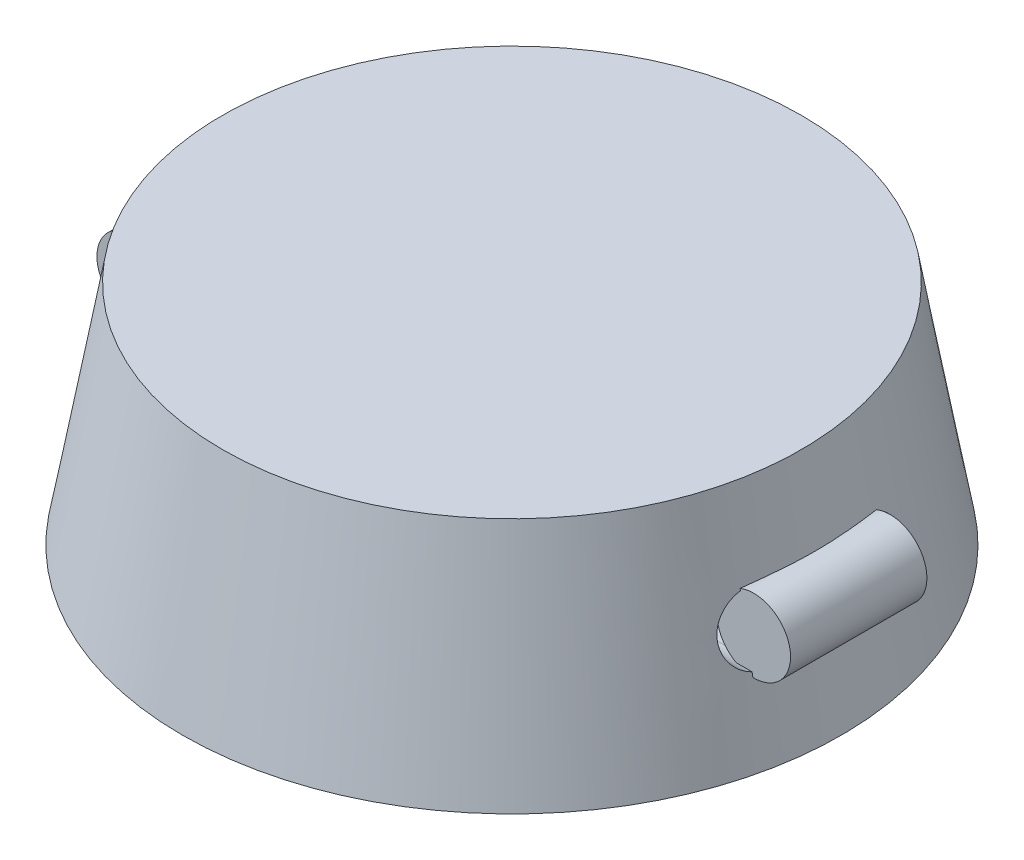
SolidWorks part; units mm, degrees
ref_plane "Front Plane" through (0, 0, 0) normal (0, 0, 1) x (1, 0, 0)
ref_plane "Top Plane" through (0, 0, 0) normal (0, 1, 0) x (1, 0, 0)
ref_plane "Right Plane" through (0, 0, 0) normal (1, 0, 0) x (0, 0, -1)
sketch "Sketch1" plane through (0, 0, 0) normal (0, 1, 0) x (1, 0, 0)
  circle A0 centre (0, 0) radius 72.5
  dimension "D1" = 145
extrude "Boss-Extrude1" add sketch "Sketch1" along normal blind 50 draft 10
sketch "Sketch2" plane through (0, 0, 0) normal (1, 0, 0) x (0, 0, -1)
  line L0 (-12.5278, 24.3146) -> (12.4722, 24.3146) construction
  line L1 (-12.5278, 31.8146) -> (12.4722, 31.8146)
  line L2 (-12.5278, 16.8146) -> (12.4722, 16.8146)
  arc A0 (-12.5278, 31.8146) -> (-12.5278, 16.8146) centre (-12.5278, 24.3146) ccw
  arc A1 (12.4722, 16.8146) -> (12.4722, 31.8146) centre (12.4722, 24.3146) ccw
  point P2 (-0.0278, 24.3146)
  dimension "D1" = 15
  dimension "D2" = 25
extrude "Cut-Extrude1" cut sketch "Sketch2" against normal blind 87 and the other way blind 94
sketch "Sketch3" plane through (0, 0, 0) normal (0, 0, 1) x (1, 0, 0)
  circle A0 centre (68.2127, 24.3146) radius 8.0752
  point P2 (69.2, 24.541)
extrude "Boss-Extrude5" add sketch "Sketch3" along normal blind 15 and the other way blind 15
mirror "Mirror1" about plane through (0, 0, 0) normal (1, 0, 0) of "Boss-Extrude5"
